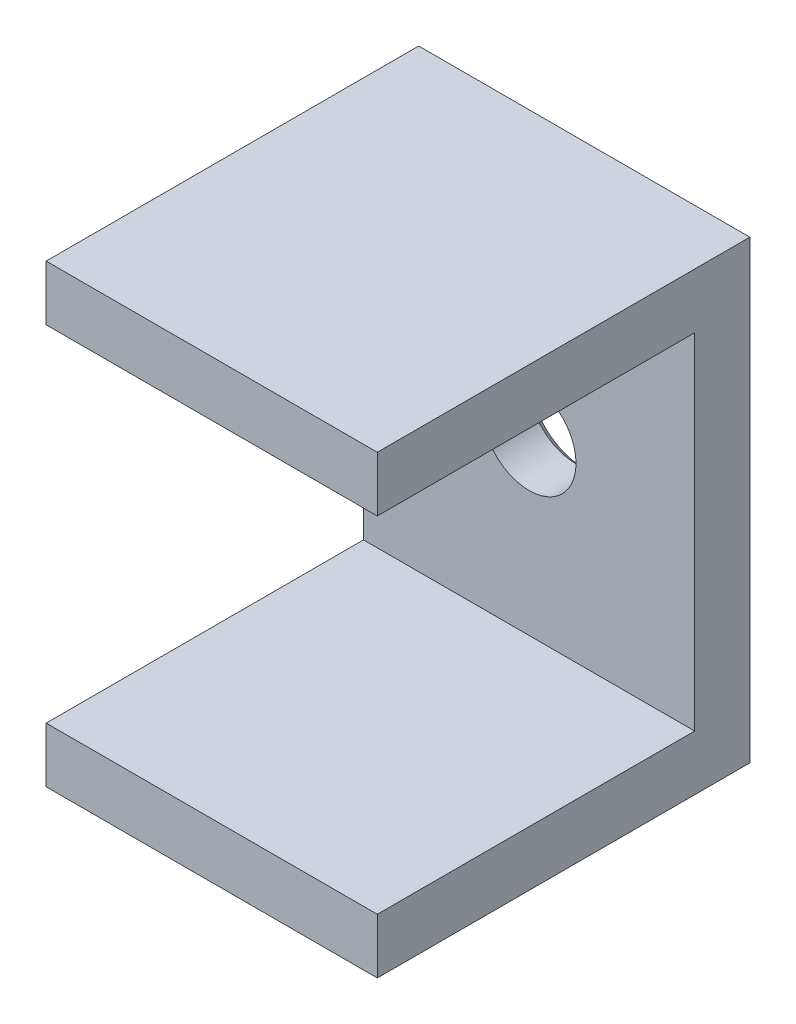
SolidWorks part; units mm, degrees
ref_plane "前视基准面" through (0, 0, 0) normal (0, 0, 1) x (1, 0, 0)
ref_plane "上视基准面" through (0, 0, 0) normal (0, 1, 0) x (1, 0, 0)
ref_plane "右视基准面" through (0, 0, 0) normal (1, 0, 0) x (0, 0, -1)
other "Configuration Table"
sketch "草图1" plane through (0, 0, 0) normal (0, 1, 0) x (1, 0, 0)
  line L1 (-12, 13.5) -> (12, 13.5)
  line L2 (-12, 13.5) -> (-12, -13.5)
  line L3 (-12, -13.5) -> (12, -13.5)
  line L4 (12, 13.5) -> (12, -13.5)
  line L5 (-12, 13.5) -> (12, -13.5) construction
  line L6 (-12, -13.5) -> (12, 13.5) construction
  point P0 (0, 0)
  dimension "D1" = 27
  dimension "D2" = 24
extrude "凸台-拉伸1" add sketch "草图1" along normal blind 33
sketch "草图3" plane through (0, 0, 13.5) normal (0, 0, 1) x (1, 0, 0)
  line L0 (-12, 29) -> (12, 29)
  line L1 (-12, 33) -> (-12, 0) construction
  line L2 (12, 33) -> (12, 0) construction
  line L3 (12, 29) -> (12, 4)
  line L4 (12, 4) -> (-12, 4)
  line L5 (-12, 4) -> (-12, 29)
  line L6 (-12, 0) -> (12, 0) construction
  line L7 (-12, 33) -> (12, 33) construction
  dimension "D1" = 4
  dimension "D2" = 4
  dimension "D3" = 25
extrude "切除-拉伸1" cut sketch "草图3" against normal blind 23
sketch "草图4" plane through (0, 0, -13.5) normal (0, 0, -1) x (-1, 0, 0)
  line L0 (-12, 33) -> (12, 0) construction
  line L1 (-12, 0) -> (12, 33) construction
  point P8 (0, 16.5)
hole_wizard "M8 螺纹孔1" positions "草图4" profile "草图5" tap size "M8" standard "GB" end condition up to next
sketch "草图5" plane through (0, 16.5, -13.5) normal (1, 0, 0) x (0, 1, 0)
  line L0 (0, 0) -> (0, 4)
  line L1 (0, 4) -> (3.4, 4)
  line L2 (3.4, 4) -> (3.4, 0.625)
  line L3 (3.4, 0.625) -> (4.025, 0)
  line L5 (4.025, 0) -> (0, 0)
  line L6 (-3.4, 0.625) -> (-4.025, 0) construction
  line L11 (0, -6.35) -> (0, 107.95) construction
  dimension "通孔螺纹孔钻头直径" = 6.8
  dimension "通孔螺纹孔钻头深度" = 4
  dimension "近端锥形沉头孔直径" = 8.05
  dimension "近端锥形沉头孔角度" = 90
cosmetic thread "孔螺蚊线1" parameters "D2"=8
